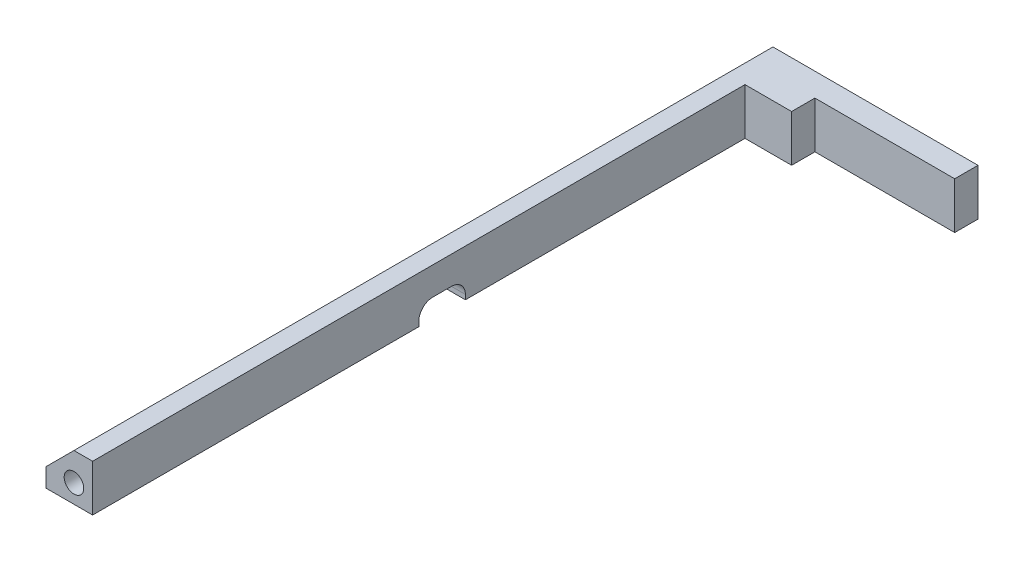
SolidWorks part; units mm, degrees
material "ABS"
ref_plane "Płaszczyzna przednia" through (0, 0, 0) normal (0, 0, 1) x (1, 0, 0)
ref_plane "Płaszczyzna górna" through (0, 0, 0) normal (0, 1, 0) x (1, 0, 0)
ref_plane "Płaszczyzna prawa" through (0, 0, 0) normal (1, 0, 0) x (0, 0, -1)
sketch "Szkic1" plane through (0, 0, 0) normal (0, 1, 0) x (1, 0, 0)
  line L0 (0, 0) -> (0, 150)
  line L1 (0, 150) -> (50, 150)
  line L2 (50, 150) -> (50, 145)
  line L3 (50, 145) -> (20, 145)
  line L4 (20, 145) -> (20, 140)
  line L5 (20, 140) -> (10, 140)
  line L6 (10, 140) -> (10, 0)
  line L7 (10, 0) -> (0, 0)
  dimension "D1" = 140
  dimension "D2" = 5
  dimension "D3" = 5
  dimension "D5" = 10
  dimension "D6" = 10
  dimension "30" = 30
extrude "Dodanie-wyciągnięcie1" add sketch "Szkic1" along normal blind 10
sketch "Szkic2" plane through (0, 0, 0) normal (0, -1, 0) x (1, 0, 0)
  line L0 (0, 0) -> (0, -27) construction
  line L1 (0, -150) -> (0, 0) construction
  line L2 (0, -27) -> (7.2, -27) construction
  line L3 (7.2, -27) -> (7.2, -123) construction
  circle A0 centre (7.2, -27) radius 2.1
  circle A1 centre (7.2, -123) radius 2.1
  dimension "D2" = 4.2
  dimension "D4" = 4.2
  dimension "D1" = 27
  dimension "D3" = 96
  dimension "D5" = 7.2
extrude "Wytnij-wyciągnięcie1" cut sketch "Szkic2" against normal blind 4
sketch "Szkic3" plane through (0, 0, 0) normal (0, 0, 1) x (1, 0, 0)
  line L0 (0, 0) -> (6, 0) construction
  line L1 (0, 0) -> (10, 0) construction
  line L2 (6, 0) -> (6, 4) construction
  circle A0 centre (6, 4) radius 2.1
  dimension "D3" = 4.2
extrude "Wytnij-wyciągnięcie2" cut sketch "Szkic3" against normal blind 4
chamfer "Sfazowanie1" distance 6 angle 45 1 edges at (0, 10, -75)
sketch "Szkic4" plane through (0, 0, 0) normal (0, -1, 0) x (1, 0, 0)
  line L0 (0, 0) -> (0, -75) construction
  line L1 (0, -150) -> (0, 0) construction
  line L7 (0, -70) -> (0, -80)
  line L8 (0, -80) -> (10, -80)
  line L9 (10, 0) -> (10, -140) construction
  line L10 (10, -80) -> (10, -70)
  line L11 (10, -70) -> (0, -70)
  point P8 (0, -75)
  dimension "D2" = 75
  dimension "D1" = 10
extrude "Wytnij-wyciągnięcie3" cut sketch "Szkic4" against normal blind 4
fillet "Zaokrąglenie1" radius 3 2 edges at (5, 4, -70) (5, 4, -80)
equation "\"Length\"=140"
equation "\"D1@Szkic1\"=\"Length\""
equation "\"Width\"=10"
equation "\"D6@Szkic1\"=\"Width\""
equation "\"D3@Szkic1\"=\"Width\"/2"
equation "\"D2@Szkic1\"=\"Width\"/2"
equation "\"D1@Szkic2\"=(\"Length\"+\"Width\"-96)/2"
equation "\"InsertDiameter\"=4.2"
equation "\"D2@Szkic2\"=\"InsertDiameter\""
equation "\"D4@Szkic2\"=\"InsertDiameter\""
equation "\"D3@Szkic3\"=\"InsertDiameter\""
equation "\"D1@Szkic3\"=\"Width\"/2+1"
equation "\"D2@Szkic3\"=\"Width\"/2-1"
equation "\"StrapSize\"=10"
equation "\"D2@Szkic4\"=(\"Length\"+\"Width\")/2"
equation "\"D1@Szkic4\"=\"StrapSize\""
